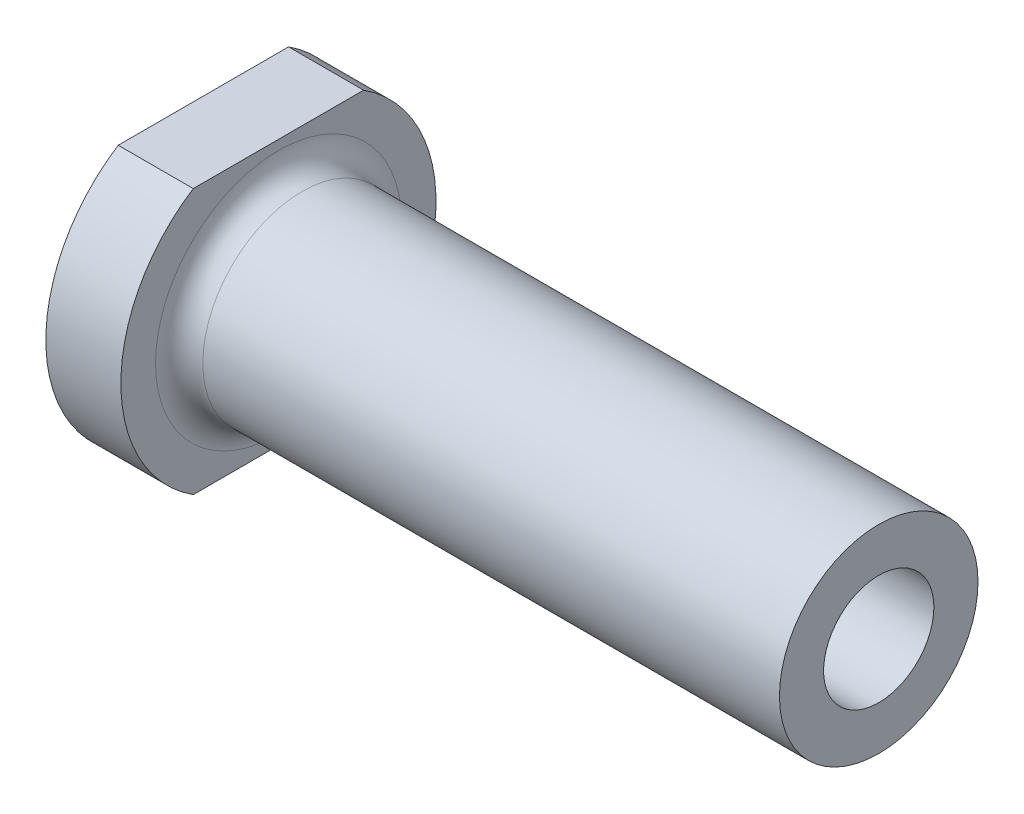
SolidWorks part; units mm, degrees
material "Ti-6Al-4VSolution treated and aged (SS)"
ref_plane "Front Plane" through (0, 0, 0) normal (0, 0, 1) x (1, 0, 0)
ref_plane "Top Plane" through (0, 0, 0) normal (0, 1, 0) x (1, 0, 0)
ref_plane "Right Plane" through (0, 0, 0) normal (1, 0, 0) x (0, 0, -1)
sketch "Sketch1" plane through (0, 0, 0) normal (0, 0, 1) x (1, 0, 0)
  line L0 (0, 0) -> (-17.6508, 0) construction
  line L1 (0, 0) -> (42.8625, 0)
  line L2 (42.8625, 0) -> (42.8625, 6.3)
  line L3 (42.8625, 6.3) -> (4.7625, 6.3)
  line L4 (4.7625, 6.3) -> (4.7625, 10)
  line L5 (4.7625, 10) -> (0, 10)
  line L6 (0, 10) -> (0, 0)
  dimension "D1" = 12.6
  dimension "D2" = 42.8625
  dimension "D3" = 4.7625
  dimension "D4" = 20
revolve "Revolve1" add sketch "Sketch1" angle 360 about L0
fillet "Fillet1" radius 1.5 1 edges at (4.7625, 0, -6.3)
hole_wizard "5/16-18 MAKE SURE TO CHANGE THIS" positions "Sketch2" profile "Sketch3" tap size "M8x1.0" standard "ANSI Metric" end condition through all
sketch "Sketch2" plane through (42.8625, 0, 0) normal (1, 0, 0) x (0, 0, -1)
  point P0 (0, 0)
sketch "Sketch3" plane through (42.8625, 0, 0) normal (0, 1, 0) x (0, 0, -1)
  line L0 (0, 0) -> (0, 42.8625)
  line L1 (0, 42.8625) -> (3.5, 42.8625)
  line L2 (3.5, 42.8625) -> (3.5, 0)
  line L5 (3.5, 0) -> (0, 0)
  line L11 (0, -6.35) -> (0, 107.95) construction
  dimension "Thru Tap Drill Dia." = 7
  dimension "Thru Tap Drill Depth" = 42.8625
cosmetic thread "Hole Thread1"
sketch "Sketch4" plane through (0, 0, 0) normal (-1, 0, 0) x (0, 0, 1)
  line L0 (-5.4065, 8.4125) -> (5.4065, 8.4125)
  line L5 (5.4065, -8.4125) -> (-5.4065, -8.4125)
  arc A1 (5.4065, 8.4125) -> (-5.4065, 8.4125) centre (0, 0) ccw
  circle A2 centre (0, 0) radius 10
  arc A3 (-5.4065, -8.4125) -> (5.4065, -8.4125) centre (0, 0) ccw
  point P4 (0, 10)
  dimension "D1" = 0
  dimension "D2" = 1.5875
extrude "Cut-Extrude1" cut sketch "Sketch4" against normal through all
equation "\"D4@Sketch1\"=20mm"
equation "\"D1@Sketch1\"=0.500000in-0.1mm"
